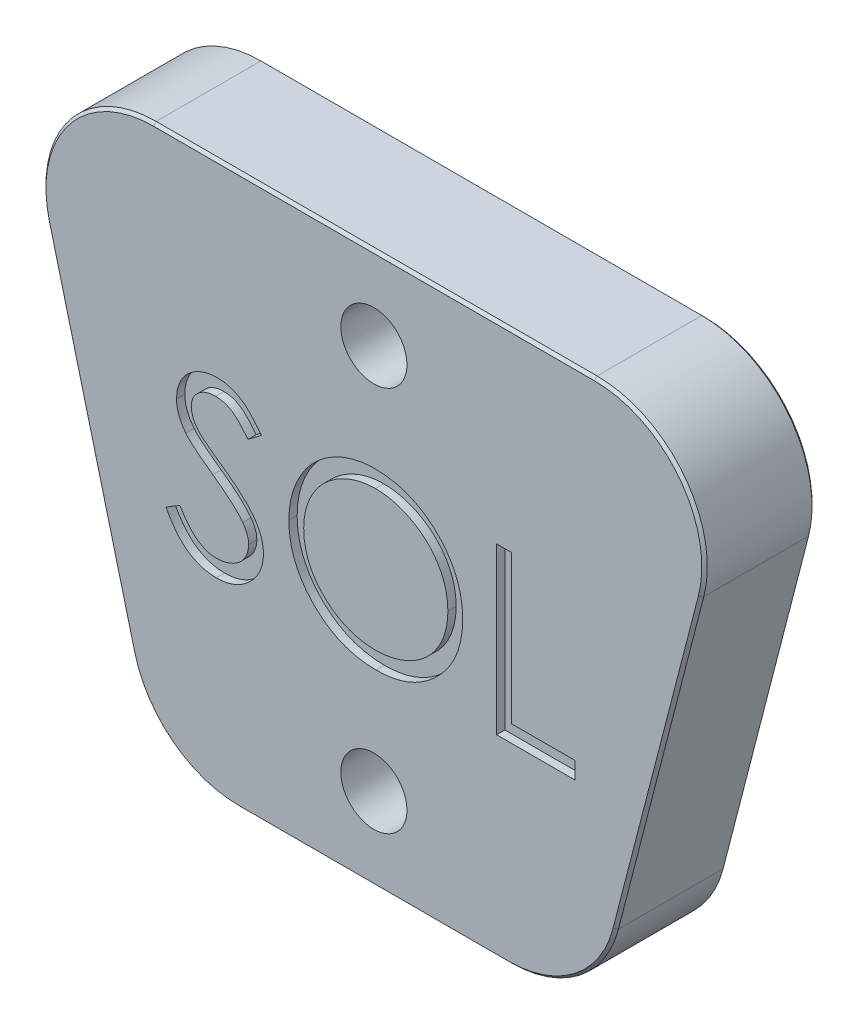
SolidWorks part; units mm, degrees
ref_plane "Front Plane" through (0, 0, 0) normal (0, 0, 1) x (1, 0, 0)
ref_plane "Top Plane" through (0, 0, 0) normal (0, 1, 0) x (1, 0, 0)
ref_plane "Right Plane" through (0, 0, 0) normal (1, 0, 0) x (0, 0, -1)
sketch "Sketch2" plane through (0, 0, 0) normal (0, 0, 1) x (1, 0, 0)
  line L0 (20, -80) -> (100, -80)
  line L6 (100, 20) -> (20, 20)
  line L8 (0.6351, -5) -> (20, -80)
  line L9 (119.3649, -5) -> (100, -80)
  line L10 (120, 23.0116) -> (120, 0)
  line L11 (0, 0) -> (0, 50.4461)
  line L12 (60, 20) -> (60, -80) construction
  arc A4 (119.3649, -5) -> (100, 20) centre (100, 0) ccw
  arc A5 (0.6351, -5) -> (20, 20) centre (20, 0) cw
  point P2 (120, 23.0116)
  point P4 (27.6124, -80)
  point P7 (15.5222, -80)
  point P12 (120, 23.0116)
  point P15 (0, 0)
  point P21 (0, 0)
  dimension "D3" = 20
  dimension "D1" = 120
  dimension "D2" = 100
  dimension "D4" = 80
extrude "Boss-Extrude1" add sketch "Sketch2" along normal blind 20 contours A5 L8 L0 L9 A4 L6 | L12 L6 A5 L8 L0 region at (33.9449, -27.1175, 0) region at (86.0551, -27.1175, 0)
fillet "Fillet2" radius 20 2 edges at (20, -80, 10) (100, -80, 10)
sketch "Sketch10" plane through (0, 0, 20) normal (0, 0, 1) x (1, 0, 0)
  line L0 (60, 20) -> (60, -10) construction
  line L3 (60, 20) -> (60, -10) construction
  line L4 (60, -50) -> (60, -80) construction
  line L5 (60, 20) -> (60, -10) construction
  line L6 (60, -50) -> (60, -80) construction
  line L7 (100, 20) -> (20, 20) construction
  line L8 (35.4919, -80) -> (84.5081, -80) construction
  circle A1 centre (60, -65) radius 6
  circle A2 centre (60, 5) radius 6
  point P2 (0, 0)
  point P3 (0, 0)
  point P7 (0, 0)
  point P13 (0, 0)
  point P16 (60, -6.8831)
  point P17 (60, -44.1192)
  dimension "D1" = 12
  dimension "D2" = 15
  dimension "D3" = 15
extrude "Cut-Extrude6" cut sketch "Sketch10" against normal blind 12
sketch "Sketch11" plane through (0, 0, 8) normal (0, 0, 1) x (1, 0, 0)
  circle A0 centre (60, 5) radius 3.2
  circle A2 centre (60, -65) radius 3.2
  dimension "D1" = 6.4
extrude "Cut-Extrude7" cut sketch "Sketch11" against normal through all
sketch "Sketch13" plane through (0, 0, 20) normal (0, 0, 1) x (1, 0, 0)
  line L0 (35.4919, -80) -> (84.5081, -80) construction
  text T0 "SOL" font "Century Gothic" height 30
  point P1 (0, 0)
  dimension "D1" = 35
  dimension "D2" = 21.5
extrude "Cut-Extrude8" cut sketch "Sketch13" against normal blind 1.5
chamfer "Chamfer1" distance 0.5 angle 45 18 edges at (115.8114, 12.2474, 0) (4.1886, 12.2474, 0) (8.381, -35, 0) (111.619, -35, 0) (63.2, -65, 0) (63.2, 5, 0) (4.1886, 12.2474, 20) (115.8114, 12.2474, 20) (111.619, -35, 20) (8.381, -35, 20) (60, -80, 0) (60, 20, 0) (60, 20, 20) (96.7555, -75.8114, 0) (23.2445, -75.8114, 0) (60, -80, 20) (23.2445, -75.8114, 20) (96.7555, -75.8114, 20)
